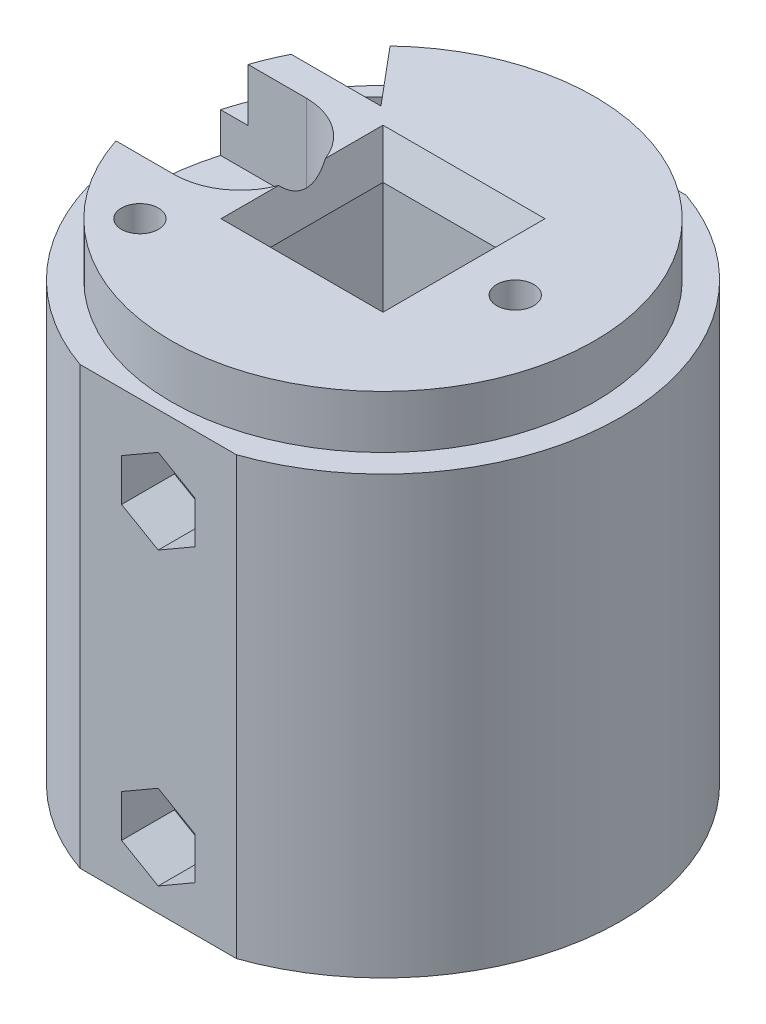
SolidWorks part; units mm, degrees
ref_plane "Спереди" through (0, 0, 0) normal (0, 0, 1) x (1, 0, 0)
ref_plane "Сверху" through (0, 0, 0) normal (0, 1, 0) x (1, 0, 0)
ref_plane "Справа" through (0, 0, 0) normal (1, 0, 0) x (0, 0, -1)
sketch "Sketch1" plane through (0, 0, 0) normal (0, 1, 0) x (1, 0, 0)
  line L0 (-5.125, 0) -> (-18, 0) construction
  line L1 (5.125, -5.125) -> (-5.125, -5.125)
  line L2 (5.125, -5.125) -> (5.125, 5.125)
  line L3 (5.125, 5.125) -> (-5.125, 5.125)
  line L4 (-5.125, -5.125) -> (-5.125, 5.125)
  line L5 (5.125, -5.125) -> (-5.125, 5.125) construction
  line L6 (5.125, 5.125) -> (-5.125, -5.125) construction
  circle A0 centre (0, 0) radius 18
  circle A1 centre (-12, 0) radius 2
  dimension "D1" = 36
  dimension "D3" = 6
  dimension "D2" = 10.25
extrude "Boss-Extrude1" add sketch "Sketch1" along normal blind 37
sketch "Sketch2" plane through (0, 37, 0) normal (0, 1, 0) x (1, 0, 0)
  line L0 (-10.8, 5) -> (-17.2916, 5)
  line L1 (-10.8, -5) -> (-17.2916, -5)
  line L2 (-5.125, 0) -> (-18, 0) construction
  line L3 (-5.125, 5.125) -> (-5.125, -5.125) construction
  circle A1 centre (0, 0) radius 18 construction
  arc A2 (-17.2916, 5) -> (-17.2916, -5) centre (0, 0) ccw
  arc A3 (-10.8, 5) -> (-10.8, -5) centre (-10.8, 0) cw
  point P12 (-5.8, 0)
  dimension "D1" = 5
extrude "Cut-Extrude1" cut sketch "Sketch2" against normal blind 7
sketch "Sketch4" plane through (0, 0, 0) normal (0, -1, 0) x (-1, 0, 0)
  line L0 (0, 0) -> (18, 21.4516) construction
  line L1 (0, 0) -> (18, -21.4516) construction
  line L2 (18, 21.4516) -> (18, -21.4516) construction
  line L3 (0, 0) -> (13.6996, 11.6756) construction
  line L4 (0, 0) -> (13.6996, -11.6756) construction
  line L5 (0, 0) -> (18, 0) construction
  line L6 (5.125, 5.125) -> (5.125, -5.125) construction
  line L7 (11.5702, 13.7888) -> (5.1423, 6.1284) construction
  line L8 (5.1423, 6.1284) -> (5.1423, -4.3826) construction
  line L9 (5.1423, -4.3826) -> (13.6996, -11.6756) construction
  line L10 (5.1423, 0.8729) -> (18.1354, 0.8729) construction
  line L12 (15.8104, 5.5479) -> (6.4604, 5.5479)
  line L13 (15.8104, 5.5479) -> (15.8104, -3.8021)
  line L14 (15.8104, -3.8021) -> (6.4604, -3.8021)
  line L15 (6.4604, 5.5479) -> (6.4604, -3.8021)
  line L16 (15.8104, 5.5479) -> (6.4604, -3.8021) construction
  line L17 (15.8104, -3.8021) -> (6.4604, 5.5479) construction
  arc A0 (13.6996, -11.6756) -> (11.5702, 13.7888) centre (0.5154, 0.0431) ccw construction
  circle A2 centre (0, 0) radius 18 construction
  point P2 (11, 0)
  point P5 (11.5702, 13.7888)
  point P7 (4.1157, 3.5076)
  point P8 (11.5702, -13.7888)
  point P11 (5.125, -6.1077)
  point P16 (11.1354, 0.8729)
  dimension "D5" = 10
  dimension "D1" = 100
  dimension "D2" = 3
  dimension "D3" = 3
  dimension "D4" = 9.35
  dimension "D6" = 7
extrude "Cut-Extrude3" cut sketch "Sketch4" against normal blind 20.4
sketch "Sketch5" plane through (0, 37, 0) normal (0, 1, 0) x (1, 0, 0)
  line L0 (0, 18) -> (0, -18) construction
  line L1 (5.9161, 17) -> (-5.9161, 17)
  line L2 (5.9161, -17) -> (-5.9161, -17)
  circle A0 centre (0, 0) radius 18 construction
  arc A1 (5.9161, 17) -> (-5.9161, 17) centre (0, 0) ccw
  arc A2 (5.9161, -17) -> (-5.9161, -17) centre (0, 0) cw
  point P11 (0, 17)
  dimension "D1" = 1
extrude "Cut-Extrude4" cut sketch "Sketch5" against normal blind 40
sketch "Sketch6" plane through (0, 0, -17) normal (0, 0, -1) x (-1, 0, 0)
  line L0 (0, 37) -> (0, 0) construction
  line L1 (5.9161, 37) -> (-5.9161, 37) construction
  line L3 (5.9161, 0) -> (-5.9161, 0) construction
  circle A0 centre (0, 27) radius 1.5
  circle A1 centre (0, 5) radius 1.5
  dimension "D1" = 3
  dimension "D2" = 10
  dimension "D3" = 5
extrude "Cut-Extrude5" cut sketch "Sketch6" against normal through all
sketch "Sketch7" plane through (0, 0, -17) normal (0, 0, -1) x (-1, 0, 0)
  circle A0 centre (0, 27) radius 3
  circle A1 centre (0, 5) radius 3
  dimension "D1" = 6
extrude "Cut-Extrude6" cut sketch "Sketch7" against normal blind 3
sketch "Sketch8" plane through (0, 0, 17) normal (0, 0, 1) x (1, 0, 0)
  line L0 (5.9161, 0) -> (5.9161, 37) construction
  line L1 (0, 23.8) -> (2.7713, 25.4)
  line L2 (2.7713, 25.4) -> (2.7713, 28.6)
  line L3 (2.7713, 28.6) -> (0, 30.2)
  line L4 (0, 30.2) -> (-2.7713, 28.6)
  line L5 (-2.7713, 28.6) -> (-2.7713, 25.4)
  line L6 (-2.7713, 25.4) -> (0, 23.8)
  line L9 (0, 1.8) -> (2.7713, 3.4)
  line L10 (2.7713, 3.4) -> (2.7713, 6.6)
  line L11 (2.7713, 6.6) -> (0, 8.2)
  line L12 (0, 8.2) -> (-2.7713, 6.6)
  line L13 (-2.7713, 6.6) -> (-2.7713, 3.4)
  line L14 (-2.7713, 3.4) -> (0, 1.8)
  circle A0 centre (0, 27) radius 3.2 construction
  circle A1 centre (0, 5) radius 3.2 construction
  dimension "D1" = 6.4
extrude "Cut-Extrude7" cut sketch "Sketch8" against normal blind 4
chamfer "Chamfer1" distance 1 angle 70 4 edges at (-5.125, 37, 0) (0, 37, -5.125) (0, 37, 5.125) (5.125, 37, 0) first distance on face at (-5.2523, 37, 0)
sketch "Sketch9" plane through (0, 0, 0) normal (0, -1, 0) x (1, 0, 0)
  line L0 (16.4542, -7.2979) -> (-16.4542, -7.2979) construction
  line L1 (-15.8104, -5.5479) -> (-6.4604, -5.5479) construction
  line L2 (-7.4542, -7.2979) -> (-15.4542, -7.2979)
  line L3 (-7.4542, -7.2979) -> (-11.6323, -12.2772)
  line L4 (5.125, -5.125) -> (-5.125, -5.125) construction
  circle A0 centre (0, 0) radius 18 construction
  arc A1 (-15.4542, -7.2979) -> (-11.6323, -12.2772) centre (0.5168, 1.0043) ccw
  point P10 (-11.4542, -7.2979)
  dimension "D8" = 18
  dimension "D1" = 1.75
  dimension "D2" = 5
  dimension "D3" = 6.5
  dimension "D4" = 50
  dimension "D5" = 8
  dimension "D6" = 2.1729
  dimension "D7" = 23.9084
extrude "Cut-Extrude8" cut sketch "Sketch9" against normal through all
sketch "Sketch12" plane through (0, 37, 0) normal (0, 1, 0) x (1, 0, 0)
  line L0 (18, 0) -> (-10.8, 0) construction
  line L1 (0, 0) -> (-12.7279, -12.7279) construction
  arc A0 (5.9161, -17) -> (5.9161, 17) centre (0, 0) ccw construction
  arc A1 (-17.2916, -5) -> (-5.9161, -17) centre (0, 0) ccw construction
  circle A2 centre (10, 0) radius 1.4
  circle A3 centre (-9.1924, -9.1924) radius 1.4
  dimension "D1" = 2.8
  dimension "D2" = 10
  dimension "D3" = 13
extrude "Cut-Extrude10" cut sketch "Sketch12" against normal blind 20
sketch "Sketch10" plane through (0, 37, 0) normal (0, 1, 0) x (1, 0, 0)
  circle A1 centre (0, 0) radius 18
  circle A2 centre (0, 0) radius 16
  arc A3 (-17.2916, -5) -> (-5.9161, -17) centre (0, 0) ccw construction
  dimension "D1" = 2
extrude "Cut-Extrude9" cut sketch "Sketch10" against normal blind 4
